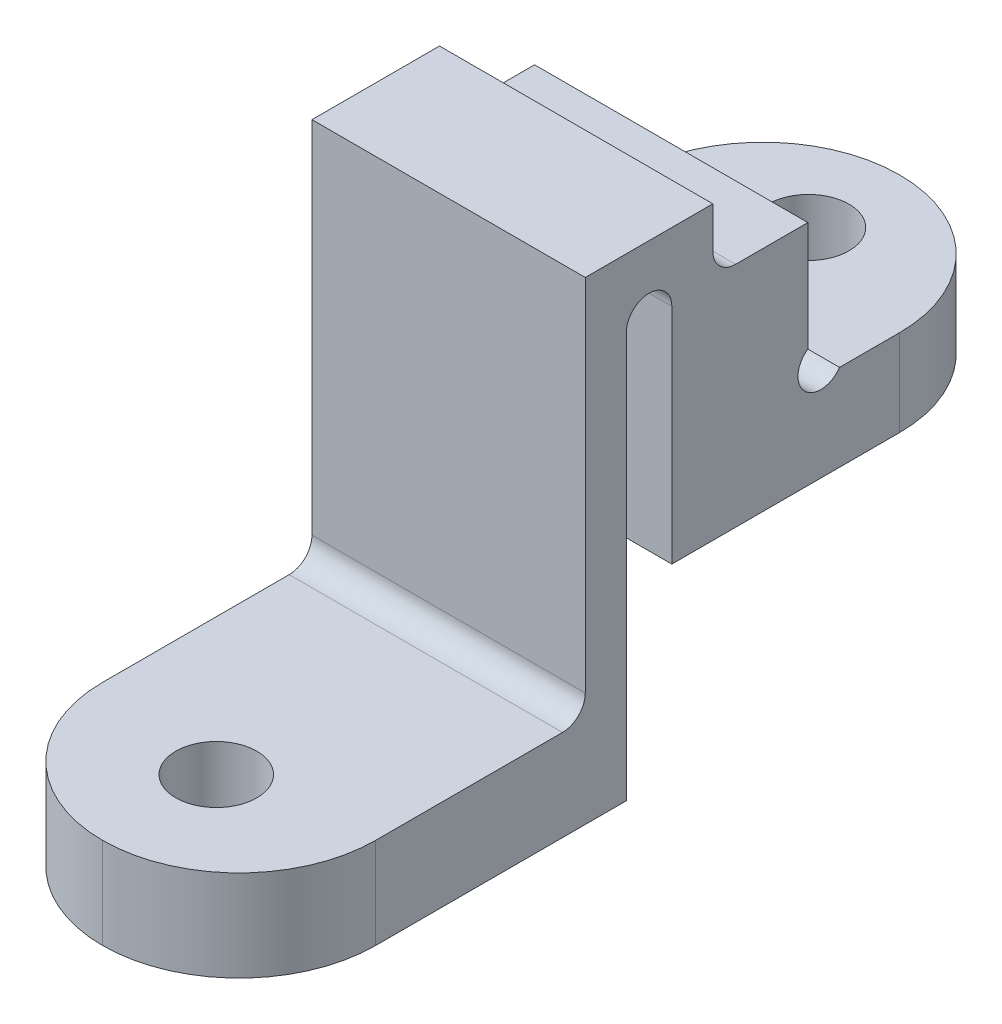
SolidWorks part; units mm, degrees
material "Copper"
ref_plane "Front Plane" through (0, 0, 0) normal (0, 0, 1) x (1, 0, 0)
ref_plane "Top Plane" through (0, 0, 0) normal (0, 1, 0) x (1, 0, 0)
ref_plane "Right Plane" through (0, 0, 0) normal (1, 0, 0) x (0, 0, -1)
ref_plane "Plane1" through (7.5, 0, 0) normal (1, 0, 0) x (0, 0, -1)
sketch "Sketch1" plane through (7.5, 0, 0) normal (1, 0, 0) x (0, 0, -1)
  line L1 (-10.5, 16.9976) -> (-10.5, 6.5976)
  line L2 (-10.5, 6.5976) -> (-2, 6.5976)
  line L3 (-2, 6.5976) -> (-2, 15.4976)
  line L4 (-1, 10.5976) -> (-1, 15.4976)
  line L7 (-1.5, 15.9976) -> (-1.5, 16.9976) construction
  line L10 (-1, 10.5976) -> (7, 10.5976)
  line L11 (7, 10.5976) -> (7, 16.9976)
  line L12 (7, 16.9976) -> (-10.5, 16.9976)
  arc A0 (-2, 15.4976) -> (-1, 15.4976) centre (-1.5, 15.4976) cw
  dimension "D1" = 8.9
  dimension "D2" = 1
  dimension "D3" = 1
  dimension "D4" = 8.5
  dimension "D5" = 8
  dimension "D6" = 5.4
extrude "Boss-Extrude1" add sketch "Sketch1" against normal blind 6
sketch "Sketch2" plane through (1.5, 0, 0) normal (-1, 0, 0) x (0, 0, 1)
  line L0 (0, 15.5) -> (0.001, 15.5)
  line L1 (0.001, 15.5) -> (0.001, 20.5)
  line L2 (0.001, 20.5) -> (0, 20.5)
  line L3 (0, 20.5) -> (0, 15.5)
extrude "Cut-Extrude1" [suppressed] cut sketch "Sketch2" against normal blind 7.5
sketch3d "3DSketch1" plane through (0, 0, 0) normal (0, 0, 1) x (1, 0, 0)
  dimension "D1" = 0.5
sketch "Sketch3" plane through (1.5, 0, 0) normal (-1, 0, 0) x (0, 0, 1)
  line L0 (2.9, 20.4976) -> (2.9, 12.0976)
  line L1 (2.9, 12.0976) -> (10.5, 12.0976)
  line L2 (10.5, 12.0976) -> (10.5, 20.4976)
  line L3 (10.5, 20.4976) -> (2.9, 20.4976)
  line L4 (1.5, 20.4976) -> (1.5, 19.5006) construction
  line L5 (-7, 16.9976) -> (10.5, 16.9976) construction
  line L6 (-7.5, 20.4976) -> (0.1, 20.4976)
  line L7 (-7.5, 15.5976) -> (-7.5, 20.4976)
  line L8 (0.1, 15.5976) -> (-7.5, 15.5976)
  line L9 (0.1, 20.4976) -> (0.1, 15.5976)
  dimension "D1" = 4.9
  dimension "D2" = 8.4
  dimension "D3" = 7.6
  dimension "D4" = 3.5
extrude "Cut-Extrude2" cut sketch "Sketch3" against normal through all
sketch "Sketch4" plane through (1.5, 0, 0) normal (-1, 0, 0) x (0, 0, 1)
  line L0 (10.5, 12.0976) -> (2.9, 12.0976)
  line L1 (2.9, 12.0976) -> (10.5, 12.0976) construction
  line L2 (2.9, 12.0976) -> (2.9, 8.5976)
  line L3 (2.9, 8.5976) -> (10.5, 8.5976)
  line L4 (1.5, 20.4976) -> (1.5, 15.9976) construction
  line L5 (-1.9863, 12.4976) -> (-1.9863, 15.5976)
  line L6 (-7.4863, 15.5976) -> (-1.9863, 15.5976)
  line L7 (-7.4863, 12.4976) -> (-7.4863, 15.5976)
  line L8 (-1.9863, 12.4976) -> (-7.4863, 12.4976)
  line L10 (-7, 15.5976) -> (0.1, 15.5976) construction
  line L11 (10.5, 12.0976) -> (10.5, 6.5976) construction
  line L12 (10.5, 8.5976) -> (10.5, 12.0976)
  line L14 (-1.9863, 15.5976) -> (-1.9863, 12.4976) construction
  line L15 (0.1, 15.5976) -> (0.1, 16.9976) construction
  arc A0 (2, 15.4976) -> (1, 15.4976) centre (1.5, 15.4976) ccw construction
  dimension "D1" = 3.1
  dimension "D2" = 0
  dimension "D3" = 3.5
  dimension "D4" = 7.6
  dimension "D5" = 5.5
  dimension "D7" = 2.0863
extrude "Cut-Extrude3" cut sketch "Sketch4" against normal through all
sketch "Sketch5" plane through (1.5, 0, 0) normal (-1, 0, 0) x (0, 0, 1)
  line L0 (1, 13.1) -> (0.999, 13.1)
  line L1 (0.999, 13.1) -> (0.999, 9.1)
  line L2 (0.999, 9.1) -> (1, 9.1)
  line L3 (1, 9.1) -> (1, 13.1)
  dimension "D1" = 2.5024
extrude "Cut-Extrude4" [suppressed] cut sketch "Sketch5" against normal blind 7.5
sketch "Sketch6" plane through (1.5, 0, 0) normal (-1, 0, 0) x (0, 0, 1)
  line L0 (0, 0.5) -> (0.001, 0.5)
  line L1 (0.001, 0.5) -> (0.001, 4.5)
  line L2 (0.001, 4.5) -> (0, 4.5)
  line L3 (0, 4.5) -> (0, 0.5)
extrude "Cut-Extrude5" [suppressed] cut sketch "Sketch6" against normal blind 7.5
hole_wizard "#30 (0.1285) Diameter Hole1" [suppressed] positions "Sketch8" profile "Sketch7" hole size "#30" standard "ANSI Inch"
sketch "Sketch8" [suppressed] plane through (0, 0, 0.001) normal (0, 0, -1) x (-1, 0, 0)
  point P0 (-3.75, 2.5)
sketch "Sketch7" plane through (3.75, 2.5, 0.001) normal (1, 0, 0) x (0, 1, 0)
  line L0 (0, 0) -> (0, 10.499)
  line L1 (0, 10.499) -> (1.6319, 10.499)
  line L2 (1.6319, 10.499) -> (1.6319, 0)
  line L5 (1.6319, 0) -> (0, 0)
  line L11 (0, -6.35) -> (0, 107.95) construction
  dimension "Thru Hole Dia." = 3.2639
  dimension "Thru Hole Depth" = 10.499
fillet "Fillet1" [suppressed] radius 0.5
fillet "Fillet2" radius 3 4 edges at (1.5, 7.5976, 10.5) (7.5, 7.5976, 10.5) (7.5, 11.5476, -7) (1.5, 11.5476, -7) tangent propagation no
hole_wizard "#2-56 Tapped Hole1" positions "Sketch11" profile "Sketch12" tap size "#2-56" standard "ANSI Inch" end condition through all
sketch "Sketch11" plane through (0, 8.5976, 0) normal (0, 1, 0) x (1, 0, 0)
  line L6 (4.5, 7) -> (4.5, -10.5) construction
  point P35 (4.5, -8)
  dimension "D2" = 2.5
sketch "Sketch12" plane through (4.5, 8.5976, 8) normal (1, 0, 0) x (0, 0, 1)
  line L0 (0, 0) -> (0, 2)
  line L1 (0, 2) -> (0.889, 2)
  line L2 (0.889, 2) -> (0.889, 0)
  line L5 (0.889, 0) -> (0, 0)
  line L11 (0, -6.35) -> (0, 107.95) construction
  dimension "Thread Major Dia." = 1.778
  dimension "Thru Tap Drill Depth" = 2
fillet "Fillet3" radius 0.5 2 edges at (4.5, 15.5976, 0.1) (4.5, 8.5976, 2.9)
hole_wizard "#2-56 Tapped Hole2" positions "Sketch17" profile "Sketch18" tap size "#2-56" standard "ANSI Inch" end condition through all
sketch "Sketch17" plane through (0, 12.4976, 0) normal (0, 1, 0) x (1, 0, 0)
  line L0 (4.5, 1.9863) -> (4.5, 7) construction
  line L4 (7.5, 1.9863) -> (1.5, 1.9863) construction
  point P0 (4.5, 5)
  dimension "D1" = 2
sketch "Sketch18" plane through (4.5, 12.4976, -5) normal (1, 0, 0) x (0, 0, 1)
  line L0 (0, 0) -> (0, 5.9)
  line L1 (0, 5.9) -> (0.889, 5.9)
  line L2 (0.889, 5.9) -> (0.889, 0)
  line L5 (0.889, 0) -> (0, 0)
  line L11 (0, -6.35) -> (0, 107.95) construction
  dimension "Thread Major Dia." = 1.778
  dimension "Thru Tap Drill Depth" = 5.9
sketch "Sketch19" plane through (7.5, 0, 0) normal (1, 0, 0) x (0, 0, -1)
  line L0 (1.9863, 12.4976) -> (2.2691, 12.7804) construction
  line L1 (1.9863, 12.4976) -> (1.9863, 15.5976) construction
  circle A0 centre (2.2691, 12.7804) radius 0.5
  dimension "D1" = 0.4
  dimension "D3" = 1
  dimension "D2" = 45
extrude "Cut-Extrude6" cut sketch "Sketch19" against normal through all
